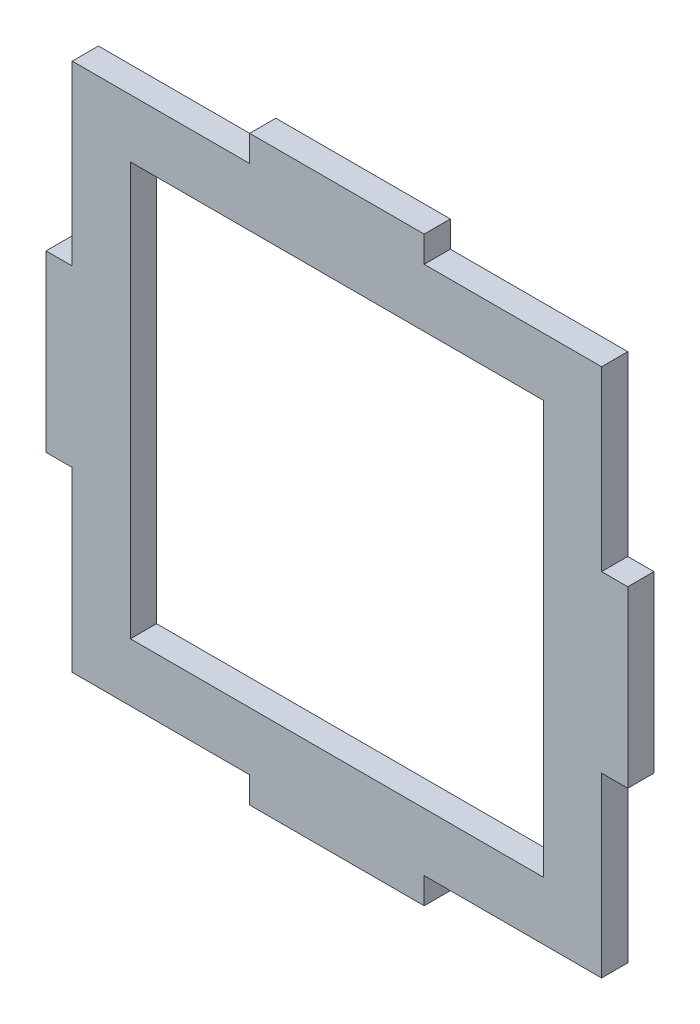
SolidWorks part; units mm, degrees
ref_plane "Front Plane" through (0, 0, 0) normal (0, 0, 1) x (1, 0, 0)
ref_plane "Top Plane" through (0, 0, 0) normal (0, 1, 0) x (1, 0, 0)
ref_plane "Right Plane" through (0, 0, 0) normal (1, 0, 0) x (0, 0, -1)
sketch "Sketch3" plane through (0, 0, 0) normal (0, 0, 1) x (1, 0, 0)
  line L0 (60.5, 91) -> (91, 91)
  line L1 (0, 0) -> (30.5, 0)
  line L2 (0, 0) -> (0, 30.5)
  line L3 (0, 91) -> (30.5, 91)
  line L4 (91, 0) -> (91, 30.5)
  line L5 (91, 60.5) -> (91, 91)
  line L6 (30.5, 91) -> (30.5, 95.5)
  line L7 (30.5, 95.5) -> (60.5, 95.5)
  line L8 (60.5, 91) -> (60.5, 95.5)
  line L9 (91, 60.5) -> (95.5, 60.5)
  line L10 (0, 60.5) -> (0, 91)
  line L11 (91, 30.5) -> (95.5, 30.5)
  line L12 (95.5, 60.5) -> (95.5, 30.5)
  line L14 (60.5, 0) -> (60.5, -4.5)
  line L15 (60.5, -4.5) -> (30.5, -4.5)
  line L16 (30.5, 0) -> (30.5, -4.5)
  line L17 (0, 60.5) -> (-4.5, 60.5)
  line L18 (60.5, 0) -> (91, 0)
  line L19 (0, 30.5) -> (-4.5, 30.5)
  line L20 (-4.5, 60.5) -> (-4.5, 30.5)
  dimension "D1" = 4.5
  dimension "D2" = 91
  dimension "D3" = 30
extrude "Boss-Extrude2" add sketch "Sketch3" along normal blind 4.5
sketch "Sketch4" plane through (0, 0, 4.5) normal (0, 0, 1) x (1, 0, 0)
  line L0 (15.25, 91) -> (15.25, 81) construction
  line L1 (10, 10) -> (81, 10)
  line L2 (10, 10) -> (10, 81)
  line L3 (10, 81) -> (81, 81)
  line L4 (81, 10) -> (81, 81)
  line L5 (30.5, 91) -> (0, 91) construction
  line L6 (0, 75.75) -> (10, 75.75) construction
  line L7 (0, 91) -> (0, 60.5) construction
  line L8 (19.9291, 0) -> (19.9291, 10) construction
  line L9 (0, 0) -> (30.5, 0) construction
  line L10 (81, 22.9589) -> (91, 22.9589) construction
  line L11 (91, 0) -> (91, 30.5) construction
  dimension "D1" = 10
extrude "Cut-Extrude1" cut sketch "Sketch4" against normal through all
equation "\"mdf\"=\"mdf@fmv1.assembly\""
equation "\"D1@Sketch3\" = \"mdf\""
equation "\"D2@Sketch3\" = 100-2*\"mdf\""
equation "\"D1@Boss-Extrude2\"=\"mdf\""
equation "\"D1@Sketch4\" = 10"
